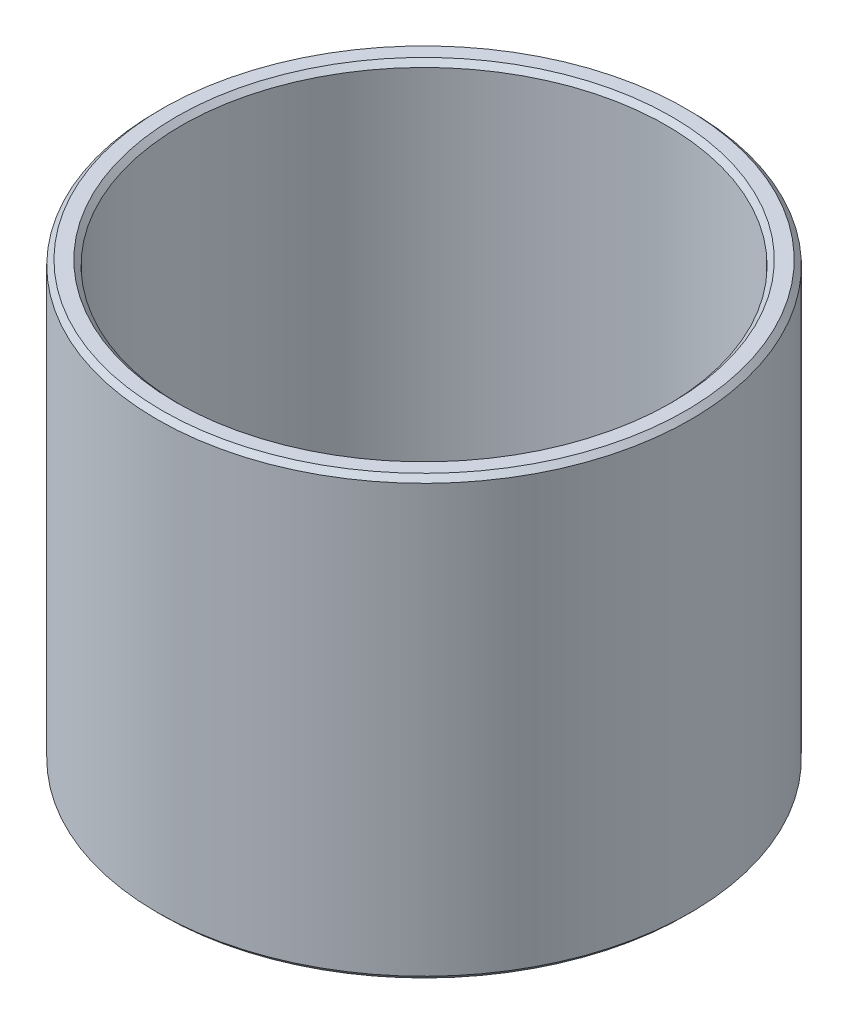
SolidWorks part; units mm, degrees
ref_plane "Front Plane" through (0, 0, 0) normal (0, 0, 1) x (1, 0, 0)
ref_plane "Top Plane" through (0, 0, 0) normal (0, 1, 0) x (1, 0, 0)
ref_plane "Right Plane" through (0, 0, 0) normal (1, 0, 0) x (0, 0, -1)
sketch "Sketch1" plane through (0, 0, 0) normal (0, 1, 0) x (1, 0, 0)
  circle A0 centre (0, 0) radius 47.5
  dimension "SLEEVE_OD" = 95
extrude "Boss-Extrude1" add sketch "Sketch1" along normal blind 77.8093
sketch "Sketch2" plane through (0, 0, 0) normal (0, 1, 0) x (1, 0, 0)
  circle A0 centre (0, 0) radius 43.1843
  dimension "BORE_D" = 86.3685
extrude "Cut-Extrude1" cut sketch "Sketch2" along normal through all
chamfer "Chamfer1" distance 0.907 angle 45 4 edges at (0, 77.8093, 43.1843) (0, 0, 43.1843) (0, 0, 47.5) (0, 77.8093, 47.5)
